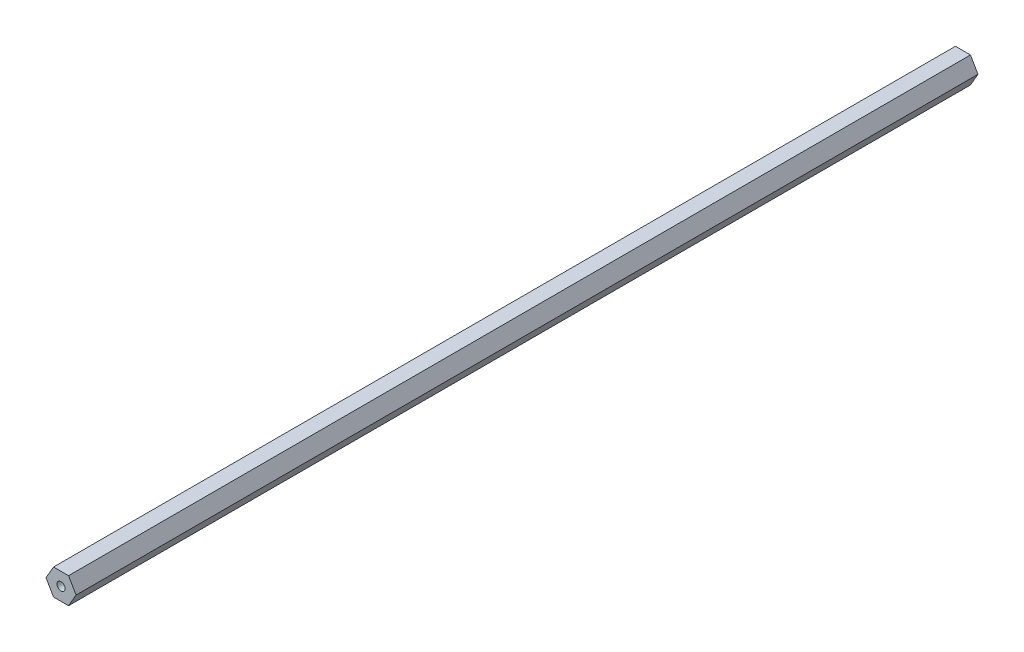
SolidWorks part; units mm, degrees
material "7075-T6 (SN)"
ref_plane "Front Plane" through (0, 0, 0) normal (0, 0, 1) x (1, 0, 0)
ref_plane "Top Plane" through (0, 0, 0) normal (0, 1, 0) x (1, 0, 0)
ref_plane "Right Plane" through (0, 0, 0) normal (1, 0, 0) x (0, 0, -1)
other "Configuration Table"
sketch "Sketch1" plane through (0, 0, 0) normal (0, 0, 1) x (1, 0, 0)
  line L1 (6.35, 0) -> (3.175, 5.4993)
  line L2 (3.175, 5.4993) -> (-3.175, 5.4993)
  line L3 (-3.175, 5.4993) -> (-6.35, 0)
  line L4 (-6.35, 0) -> (-3.175, -5.4993)
  line L5 (-3.175, -5.4993) -> (3.175, -5.4993)
  line L6 (3.175, -5.4993) -> (6.35, 0)
  circle A0 centre (0, 0) radius 5.4993 construction
  circle A1 centre (0, 0) radius 1.7145
  dimension "D2" = 3.429
  dimension "D1" = 12.7
extrude "Boss-Extrude1" add sketch "Sketch1" along normal mid plane 381
fillet "Fillet1" [suppressed] radius 0.635
equation "\"length\" = 15"
equation "\"D1@Boss-Extrude1\"=\"length\""
